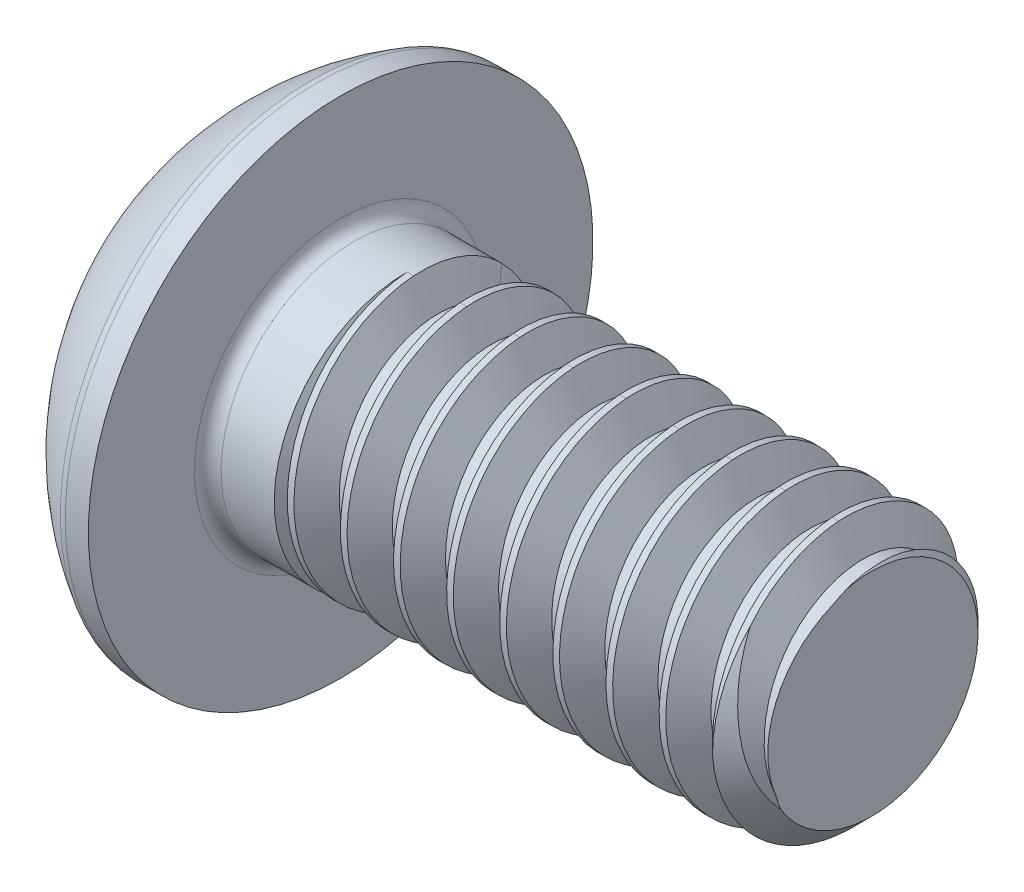
SolidWorks part; units mm, degrees
ref_plane "Alzado" through (0, 0, 0) normal (0, 0, 1) x (1, 0, 0)
ref_plane "Planta" through (0, 0, 0) normal (0, 1, 0) x (1, 0, 0)
ref_plane "Vista lateral" through (0, 0, 0) normal (1, 0, 0) x (0, 0, -1)
sketch "Croquis1" plane through (0, 0, 0) normal (0, 0, 1) x (1, 0, 0)
  line L0 (0, 0) -> (-5.4828, 0) construction
  line L1 (0, 0) -> (0, 0.8)
  line L2 (0, 0.8) -> (-0.2, 1)
  line L3 (-3.9, 1) -> (-0.2, 1)
  line L4 (-4, 1.1) -> (-4, 1.9)
  line L5 (-4, 1.9) -> (-4.2, 1.9)
  line L6 (-5.1, 0.95) -> (-5.1, 0)
  line L7 (-5.1, 0) -> (0, 0)
  arc A0 (-4, 1.1) -> (-3.9, 1) centre (-3.9, 1.1) ccw
  arc A1 (-4.2, 1.9) -> (-5.1, 0.95) centre (-3.1556, 0.0093) ccw
  dimension "D6" = 0.1
  dimension "D9" = 2.16
  dimension "D1" = 5.1
  dimension "D2" = 1.9
  dimension "D3" = 3.8
  dimension "D4" = 2
  dimension "D5" = 1.1
  dimension "D7" = 0.2
  dimension "D8" = 45
  dimension "D10" = 0.2
revolve "Revolución1" add sketch "Croquis1" angle 360 about L0
hole_wizard "Diámetro de taladro Ø1.25 (1.25)1" positions "Croquis3D1" profile "Croquis2" hole size "Ø1.25" standard "ISO"
sketch3d "Croquis3D1"
  line L0 (-5.7398, 0, 0) -> (-2.4705, 0, 0) construction
  point P0 (-5.1, 0, 0)
sketch "Croquis2" plane through (-5.1, 0, 0) normal (0, 1, 0) x (0, 0, 1)
  line L0 (0, 0) -> (0, 1.0255)
  line L1 (0, 1.0255) -> (0.625, 0.65)
  line L2 (0.625, 0.65) -> (0.625, 0)
  line L5 (0.625, 0) -> (0, 0)
  line L10 (0, 1.0255) -> (-0.625, 0.65) construction
  line L11 (0, -6.35) -> (0, 107.95) construction
  dimension "Diámetro de taladro" = 1.25
  dimension "Profundidad de taladro" = 0.65
  dimension "Ángulo de perforador" = 118
sketch "Croquis3" plane through (-5.1, 0, 0) normal (-1, 0, 0) x (0, 0, 1)
  line L1 (-0.7217, 0) -> (-0.3608, -0.625)
  line L2 (-0.3608, -0.625) -> (0.3608, -0.625)
  line L3 (0.3608, -0.625) -> (0.7217, 0)
  line L4 (0.7217, 0) -> (0.3608, 0.625)
  line L5 (0.3608, 0.625) -> (-0.3608, 0.625)
  line L6 (-0.3608, 0.625) -> (-0.7217, 0)
  circle A0 centre (0, 0) radius 0.625 construction
  circle A1 centre (0, 0) radius 0.625 construction
extrude "Cortar-Extruir1" cut sketch "Croquis3" against normal blind 0.65
fillet "Redondeo1" radius 0.1 2 edges at (-4.2, 1.9, 0) (-5.1, 0.95, 0)
fillet "Redondeo2" radius 0.05 12 edges at (-5.1, -0.625, 0) (-5.1, -0.3125, 0.5413) (-5.1, -0.3125, -0.5413) (-5.1, 0.3125, 0.5413) (-5.1, 0.3125, -0.5413) (-5.1, 0.625, 0) (-4.775, 0.625, -0.3608) (-4.775, 0, -0.7217) (-4.775, -0.625, -0.3608) (-4.775, -0.625, 0.3608) (-4.775, 0, 0.7217) (-4.775, 0.625, 0.3608)
thread "Rosca1" pitch 0.4 method cut profile "Perfil de rosca1" start angle 0, offset 1, length 0, pitch 0.4, diameter 2
ref_plane "Plano1" through (1, 0, 1) normal (0, -1, 0) x (0, 0, 1)
sketch "Perfil de rosca1" plane through (1, 0, 1) normal (0, -1, 0) x (0, 0, 1)
  line L0 (0, 0) -> (0, 0.4) construction
  line L11 (0, 0) -> (0, 0.35)
  line L12 (0, 0.35) -> (-0.2165, 0.225)
  line L13 (-0.2165, 0.225) -> (-0.2165, 0.125)
  line L15 (-0.2165, 0.125) -> (0, 0)
  line L17 (-0.2165, 0.175) -> (0, 0.175) construction
  point P2 (0, 0)
  dimension "Pitch" = 0.4
  dimension "Profile_Angle" = 60
  dimension "Profile_Land" = 0.1
  dimension "Profile_Height" = 0.2165
sketch "Croquis8" plane through (0, 0, 0) normal (0, 0, 1) x (1, 0, 0)
  line L0 (0, 0) -> (-5.4828, 0) construction
  line L2 (-4.0251, 0) -> (-4.4115, 1.1)
  line L3 (-3.9, 1) -> (-3.5, 1)
  line L4 (-4, -1.9) -> (-4, 1.9) construction
  line L8 (-3.5, 1) -> (-2.9226, 0)
  line L9 (-4, 1.1) -> (-4.4115, 1.1)
  line L12 (-4.0251, 0) -> (-2.9226, 0)
  arc A0 (-4, 1.1) -> (-3.9, 1) centre (-3.9, 1.1) ccw
  dimension "D3" = 0.1
  dimension "D2" = 0.5
  dimension "D4" = 60
  dimension "D10" = 2
revolve "Revolución2" add sketch "Croquis8" angle 360 about L0
